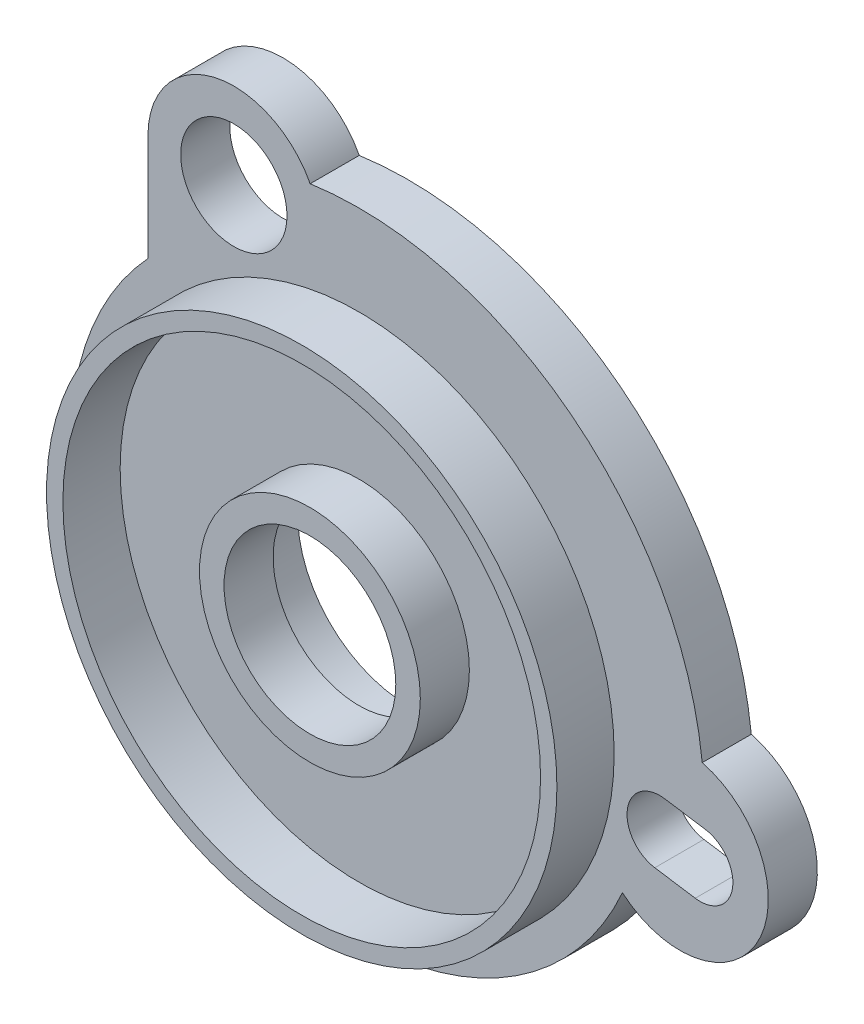
SolidWorks part; units mm, degrees
ref_plane "Спереди" through (0, 0, 0) normal (0, 0, 1) x (1, 0, 0)
ref_plane "Сверху" through (0, 0, 0) normal (0, 1, 0) x (1, 0, 0)
ref_plane "Справа" through (0, 0, 0) normal (1, 0, 0) x (0, 0, -1)
sketch "Эскиз1" plane through (0, 0, 0) normal (0, 0, 1) x (1, 0, 0)
  line L0 (15.6, 0) -> (-15.6, 0) construction
  line L1 (-12.9, 8.7721) -> (-12.9, 18.4791)
  line L5 (0, 0) -> (20.8576, -3.1889) construction
  line L6 (16.4093, -2.5088) -> (22.8347, -3.4912)
  line L7 (18.6886, -0.8341) -> (21.1599, -1.2119)
  line L9 (18.0841, -4.7881) -> (20.5554, -5.1659)
  circle A1 centre (0, 0) radius 14.6
  circle A4 centre (0, 0) radius 6.75
  circle A5 centre (0, 0) radius 5.25
  circle A6 centre (-7.65, 18.4791) radius 3.25
  arc A7 (-2.9851, 20.8878) -> (-12.9, 18.4791) centre (-7.65, 18.4791) ccw
  arc A9 (20.9823, 2.2259) -> (-2.9851, 20.8878) centre (0, 0) ccw
  arc A10 (20.5554, -5.1659) -> (21.1599, -1.2119) centre (20.8576, -3.1889) ccw
  arc A12 (18.6886, -0.8341) -> (18.0841, -4.7881) centre (18.3863, -2.8111) ccw
  arc A14 (14.7002, -5.2216) -> (19.8561, 2.3949) centre (19.622, -3) ccw
  circle A16 centre (-7.65, 18.4791) radius 5.25 construction
  arc A17 (-12.9, 11.9729) -> (16.1053, -7.0979) centre (0, 0) ccw
  circle A19 centre (0, 0) radius 17.6 construction
  circle A21 centre (0, 0) radius 15.6
  point P5 (14.9184, 4.561)
  point P20 (-2.6294, 20.0141)
  point P27 (17.6, 0)
  point P34 (21.1, 0)
  point P38 (19.622, -3)
  dimension "D5" = 13.5
  dimension "D7" = 6.5
  dimension "D12" = 4
  dimension "D10" = 28.5
  dimension "D13" = 3
  dimension "D15" = 6.5
  dimension "D2" = 2
  dimension "D6" = 1.5
extrude "Бобышка-Вытянуть1" add sketch "Эскиз1" along normal blind 3.5 contours A1 region at (4.4593, 14.488, 0)
extrude "Бобышка-Вытянуть2" add sketch "Эскиз1<4>" along normal blind 3 separate body contours A4 A5 region at (-6.5591, 0, 0)
sketch "Эскиз1<4>" plane through (0, 0, 0) normal (0, 0, 1) x (1, 0, 0) same geometry as "Эскиз1"
extrude "Бобышка-Вытянуть3" add sketch "Эскиз1<5>" against normal blind 3 separate body contours A21 A9 A7 L1 A6 A12 L7 A10 L9 | A21 L1 A17 | A1 A4 | A21 A1 region at (-7.2573, -14.3137, 0) region at (-12.403, 10.3725, 0) region at (4.4593, 14.488, 0) region at (-14.187, 0, 0)
sketch "Эскиз1<5>" plane through (0, 0, 0) normal (0, 0, 1) x (1, 0, 0) same geometry as "Эскиз1"
